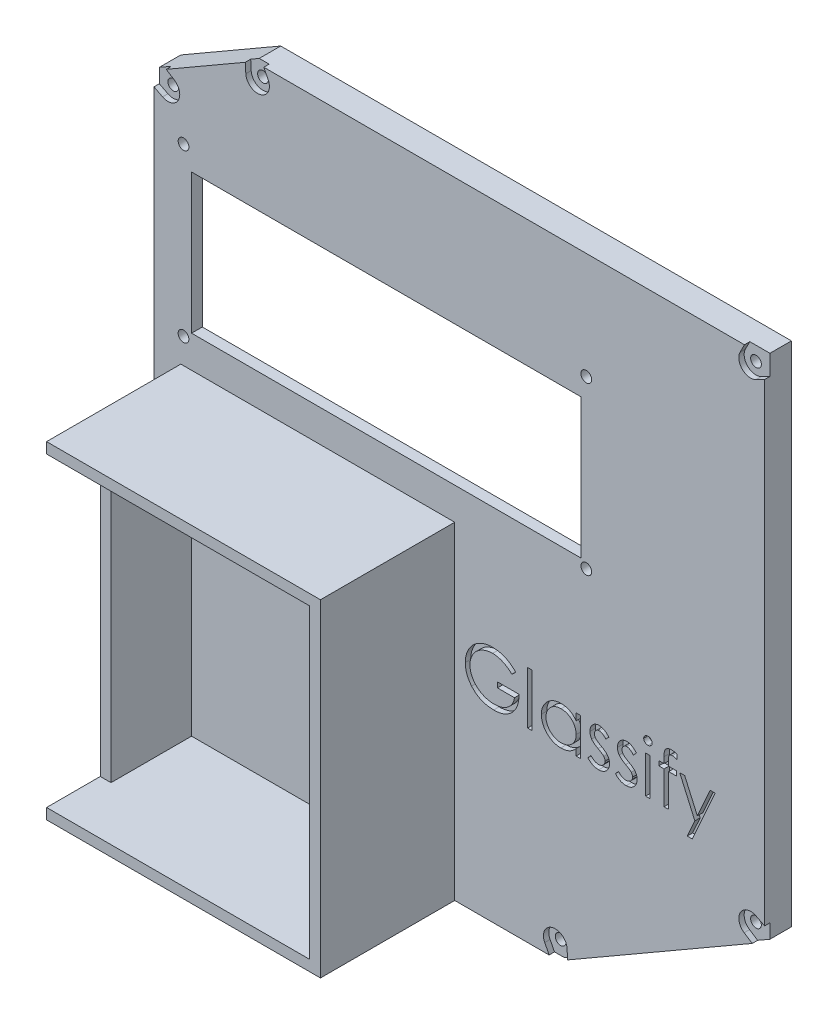
SolidWorks part; units mm, degrees
ref_plane "Front Plane" through (0, 0, 0) normal (0, 0, 1) x (1, 0, 0)
ref_plane "Top Plane" through (0, 0, 0) normal (0, 1, 0) x (1, 0, 0)
ref_plane "Right Plane" through (0, 0, 0) normal (1, 0, 0) x (0, 0, -1)
sketch "Sketch1" plane through (0, 0, 0) normal (0, 0, 1) x (1, 0, 0)
  line L6 (62.1, 287.25) -> (-33, 287.25)
  line L7 (62.1, 192.75) -> (62.1, 287.25)
  line L8 (23.8217, 170.65) -> (62.1, 192.75)
  line L9 (-51.6, 170.65) -> (23.8217, 170.65)
  line L10 (-51.6, 276.5113) -> (-51.6, 170.65)
  line L11 (-33, 287.25) -> (-51.6, 276.5113)
  line L18 (62.1, 287.25) -> (-33, 287.25)
  line L19 (62.1, 192.75) -> (62.1, 287.25)
  line L20 (23.8217, 170.65) -> (62.1, 192.75)
  line L21 (-51.6, 170.65) -> (23.8217, 170.65)
  line L22 (-51.6, 276.5113) -> (-51.6, 170.65)
  line L23 (-33, 287.25) -> (-51.6, 276.5113)
  line L24 (-50, 273.0506) -> (-50, 175.2096)
  line L25 (-34.5004, 284.5362) -> (-47.8029, 276.856)
  line L26 (57.5404, 285.65) -> (-30.3437, 285.65)
  line L27 (60.5, 196.2107) -> (60.5, 282.6904)
  line L28 (25.3221, 173.3638) -> (58.3029, 192.4053)
  line L29 (-47.0404, 172.25) -> (21.1654, 172.25)
  line L30 (-50, 273.0506) -> (-50, 175.2096)
  line L31 (-34.5004, 284.5362) -> (-47.8029, 276.856)
  line L32 (57.5404, 285.65) -> (-30.3437, 285.65)
  line L33 (60.5, 196.2107) -> (60.5, 282.6904)
  line L34 (25.3221, 173.3638) -> (58.3029, 192.4053)
  line L35 (-47.0404, 172.25) -> (21.1654, 172.25)
  circle A1 centre (-49, 173.25) radius 1
  circle A2 centre (-49, 173.25) radius 1
  circle A3 centre (-49, 275.0102) radius 1
  circle A4 centre (-49, 275.0102) radius 1
  circle A5 centre (-32.3033, 284.65) radius 1
  circle A6 centre (-32.3033, 284.65) radius 1
  circle A7 centre (59.5, 194.2511) radius 1
  circle A8 centre (59.5, 194.2511) radius 1
  circle A9 centre (59.5, 284.65) radius 1
  circle A10 centre (59.5, 284.65) radius 1
  circle A11 centre (23.125, 173.25) radius 1
  circle A12 centre (23.125, 173.25) radius 1
  arc A18 (-47.0404, 172.25) -> (-50, 175.2096) centre (-49, 173.25) ccw
  arc A19 (-50, 273.0506) -> (-47.8029, 276.856) centre (-49, 275.0102) ccw
  arc A20 (-34.5004, 284.5362) -> (-30.3437, 285.65) centre (-32.3033, 284.65) ccw
  arc A21 (57.5404, 285.65) -> (60.5, 282.6904) centre (59.5, 284.65) ccw
  arc A22 (60.5, 196.2107) -> (58.3029, 192.4053) centre (59.5, 194.2511) ccw
  arc A23 (25.3221, 173.3638) -> (21.1654, 172.25) centre (23.125, 173.25) ccw
  arc A24 (-47.0404, 172.25) -> (-50, 175.2096) centre (-49, 173.25) ccw
  arc A25 (-50, 273.0506) -> (-47.8029, 276.856) centre (-49, 275.0102) ccw
  arc A26 (-34.5004, 284.5362) -> (-30.3437, 285.65) centre (-32.3033, 284.65) ccw
  arc A27 (57.5404, 285.65) -> (60.5, 282.6904) centre (59.5, 284.65) ccw
  arc A28 (60.5, 196.2107) -> (58.3029, 192.4053) centre (59.5, 194.2511) ccw
  arc A29 (25.3221, 173.3638) -> (21.1654, 172.25) centre (23.125, 173.25) ccw
  dimension "D1" = 0
  dimension "D2" = 0
  dimension "D3" = 0
  dimension "D4" = 0
  dimension "D5" = 0
  dimension "D6" = 0
  dimension "D7" = 0
  dimension "D8" = 0
extrude "Boss-Extrude1" add sketch "Sketch1" along normal blind 3
sketch "Sketch2" plane through (0, 0, 3) normal (0, 0, 1) x (1, 0, 0)
  line L0 (23.8217, 170.65) -> (62.1, 192.75) construction
  line L1 (-51.6, 170.65) -> (23.8217, 170.65) construction
  line L2 (-51.6, 276.5113) -> (-51.6, 170.65) construction
  line L3 (-33, 287.25) -> (-51.6, 276.5113) construction
  line L4 (62.1, 287.25) -> (-33, 287.25) construction
  line L5 (62.1, 192.75) -> (62.1, 287.25) construction
  line L6 (23.8217, 170.65) -> (62.1, 192.75)
  line L7 (-51.6, 170.65) -> (23.8217, 170.65)
  line L8 (-51.6, 276.5113) -> (-51.6, 170.65)
  line L9 (-33, 287.25) -> (-51.6, 276.5113)
  line L10 (62.1, 287.25) -> (-33, 287.25)
  line L11 (62.1, 192.75) -> (62.1, 287.25)
extrude "Boss-Extrude2" add sketch "Sketch2" along normal blind 2
sketch "Sketch3" plane through (0, 0, 5) normal (0, 0, 1) x (1, 0, 0)
  line L1 (-48.6, 269.8843) -> (31.4, 269.8843) construction
  line L2 (-48.6, 269.8843) -> (-48.6, 233.8843) construction
  line L3 (-48.6, 233.8843) -> (31.4, 233.8843) construction
  line L4 (31.4, 269.8843) -> (31.4, 233.8843) construction
  line L5 (-51.6, 170.65) -> (23.8217, 170.65) construction
  line L6 (-48.6, 228.65) -> (-3.6, 228.65) construction
  line L7 (-48.6, 228.65) -> (-48.6, 173.65) construction
  line L8 (-48.6, 173.65) -> (-3.6, 173.65) construction
  line L9 (-3.6, 228.65) -> (-3.6, 173.65) construction
  line L10 (-51.6, 276.5113) -> (-51.6, 170.65) construction
  point P4 (0, 0)
  dimension "D1" = 80
  dimension "D2" = 36
  dimension "D3" = 55
  dimension "D4" = 45
  dimension "D5" = 3
  dimension "D6" = 3
sketch "Sketch4" plane through (0, 0, 3) normal (0, 0, -1) x (-1, 0, 0)
  line L1 (-27.9, 263.6343) -> (44.6, 263.6343)
  line L2 (-27.9, 263.6343) -> (-27.9, 237.6343)
  line L3 (-27.9, 237.6343) -> (44.6, 237.6343)
  line L4 (44.6, 263.6343) -> (44.6, 237.6343)
  point P4 (44.8138, 266.3299)
  point P5 (0, 0)
  point P7 (-31.4, 269.8843)
  dimension "D1" = 26
  dimension "D2" = 72.5
  dimension "D3" = 6.25
  dimension "D4" = 3.5
extrude "Cut-Extrude1" cut sketch "Sketch4" against normal up to surface (2 mm away) up to face at (1.9703, 230.8435, 5)
sketch "Sketch5" plane through (0, 0, 3) normal (0, 0, -1) x (-1, 0, 0)
  line L0 (48.6, 269.8843) -> (48.6, 233.8843) construction
  line L1 (-31.4, 269.8843) -> (-31.4, 233.8843) construction
  line L2 (48.6, 269.8843) -> (-31.4, 269.8843) construction
  line L3 (48.6, 233.8843) -> (-31.4, 233.8843) construction
  line L4 (48.6, 228.65) -> (3.6, 228.65) construction
  line L5 (48.6, 228.65) -> (48.6, 173.65) construction
  line L6 (48.6, 173.65) -> (3.6, 173.65) construction
  line L7 (3.6, 228.65) -> (3.6, 173.65) construction
  line L8 (48.6, 228.65) -> (3.6, 228.65) construction
  line L9 (48.6, 228.65) -> (48.6, 173.65) construction
  line L10 (48.6, 173.65) -> (3.6, 173.65) construction
  line L11 (3.6, 228.65) -> (3.6, 173.65) construction
  line L13 (6.1, 226.15) -> (31.1, 226.15)
  line L14 (6.1, 226.15) -> (6.1, 224.15)
  line L15 (6.1, 224.15) -> (31.1, 224.15)
  line L16 (31.1, 226.15) -> (31.1, 224.15)
  circle A0 centre (46.1, 267.3843) radius 1
  circle A1 centre (46.1, 236.3843) radius 1
  circle A2 centre (-28.9, 267.3843) radius 1
  circle A3 centre (-28.9, 236.3843) radius 1
  dimension "D5" = 2
  dimension "D1" = 2.5
  dimension "D2" = 2.5
  dimension "D3" = 2.5
  dimension "D4" = 2.5
  dimension "D6" = 25
  dimension "D7" = 2
  dimension "D8" = 2.5
  dimension "D9" = 2.5
extrude "Cut-Extrude2" cut sketch "Sketch5" against normal up to surface (2 mm away) up to face at (-8.35, 250.6343, 5)
sketch "Sketch6" plane through (0, 0, 5) normal (0, 0, 1) x (1, 0, 0)
  line L0 (-51.6, 170.65) -> (23.8217, 170.65) construction
  line L2 (-51.6, 276.5113) -> (-51.6, 170.65) construction
  line L4 (-43.6, 173.65) -> (1.4, 173.65) construction
  line L5 (1.4, 228.65) -> (1.4, 173.65) construction
  line L6 (-43.6, 228.65) -> (1.4, 228.65) construction
  line L7 (-43.6, 228.65) -> (-43.6, 173.65) construction
  line L8 (-44.6, 172.65) -> (2.4, 172.65)
  line L9 (2.4, 229.65) -> (2.4, 172.65)
  line L10 (-44.6, 229.65) -> (2.4, 229.65)
  line L11 (-44.6, 229.65) -> (-44.6, 172.65)
  line L12 (-46.6, 231.65) -> (4.4, 231.65)
  line L13 (4.4, 231.65) -> (4.4, 170.65)
  line L14 (-46.6, 170.65) -> (4.4, 170.65)
  line L15 (-46.6, 231.65) -> (-46.6, 170.65)
  dimension "D3" = 45
  dimension "D4" = 55
  dimension "D5" = 5
  dimension "D1" = 1
  dimension "D2" = 2
extrude "Boss-Extrude3" add sketch "Sketch6" along normal blind 25
sketch "Sketch7" plane through (-51.6, 0, 0) normal (-1, 0, 0) x (0, 0, 1)
  line L0 (30, 172.65) -> (30, 229.65) construction
  line L1 (30, 172.65) -> (30, 229.65)
  line L2 (30, 229.65) -> (20, 229.65)
  line L3 (20, 229.65) -> (20, 172.65)
  line L4 (20, 172.65) -> (30, 172.65)
  dimension "D1" = 10
extrude "Cut-Extrude3" cut sketch "Sketch7" against normal blind 25
sketch "Sketch8" plane through (0, 0, 5) normal (0, 0, 1) x (1, 0, 0)
  line L0 (60.5, 196.2107) -> (62.1, 195.3942)
  line L1 (62.1, 192.75) -> (62.1, 287.25) construction
  line L2 (62.1, 195.3942) -> (62.1, 192.75)
  line L3 (62.1, 192.75) -> (59.8101, 191.4279)
  line L4 (23.8217, 170.65) -> (62.1, 192.75) construction
  line L5 (59.8101, 191.4279) -> (58.3029, 192.4053)
  line L6 (25.3221, 173.3638) -> (25.415, 171.5699)
  line L7 (25.415, 171.5699) -> (23.8217, 170.65)
  line L8 (23.8217, 170.65) -> (21.9819, 170.65)
  line L9 (4.4, 170.65) -> (23.8217, 170.65) construction
  line L10 (21.9819, 170.65) -> (21.1654, 172.25)
  line L11 (-47.0404, 172.25) -> (-47.8569, 170.65)
  line L18 (-47.0404, 172.25) -> (21.1654, 172.25)
  line L19 (-50, 273.0506) -> (-50, 175.2096)
  line L20 (-34.5004, 284.5362) -> (-47.8029, 276.856)
  line L21 (57.5404, 285.65) -> (-30.3437, 285.65)
  line L22 (60.5, 196.2107) -> (60.5, 282.6904)
  line L23 (25.3221, 173.3638) -> (58.3029, 192.4053)
  line L30 (-51.6, 170.65) -> (23.8217, 170.65) construction
  line L31 (-47.8569, 170.65) -> (-51.6, 170.65)
  line L32 (-51.6, 170.65) -> (-51.6, 174.3931)
  line L33 (-51.6, 276.5113) -> (-51.6, 170.65) construction
  line L34 (-51.6, 174.3931) -> (-50, 175.2096)
  line L35 (-47.8029, 276.856) -> (-49.3101, 277.8334)
  line L36 (-33, 287.25) -> (-51.6, 276.5113) construction
  line L37 (-49.3101, 277.8334) -> (-51.6, 276.5113)
  line L38 (-51.6, 276.5113) -> (-51.6, 273.8671)
  line L39 (-51.6, 276.5113) -> (-51.6, 170.65) construction
  line L40 (-51.6, 273.8671) -> (-50, 273.0506)
  line L41 (-30.3437, 285.65) -> (-31.1602, 287.25)
  line L42 (62.1, 287.25) -> (-33, 287.25) construction
  line L43 (-31.1602, 287.25) -> (-33, 287.25)
  line L44 (-33, 287.25) -> (-34.5933, 286.3301)
  line L45 (-51.6, 276.5113) -> (-33, 287.25) construction
  line L46 (-34.5933, 286.3301) -> (-34.5004, 284.5362)
  line L47 (57.5404, 285.65) -> (58.3569, 287.25)
  line L48 (58.3569, 287.25) -> (62.1, 287.25)
  line L49 (62.1, 287.25) -> (62.1, 283.5069)
  line L50 (62.1, 283.5069) -> (60.5, 282.6904)
  circle A1 centre (-49, 275.0102) radius 1
  circle A2 centre (-49, 275.0102) radius 1
  circle A3 centre (-49, 173.25) radius 1
  circle A4 centre (-49, 173.25) radius 1
  circle A5 centre (23.125, 173.25) radius 1
  circle A6 centre (23.125, 173.25) radius 1
  circle A7 centre (59.5, 284.65) radius 1
  circle A8 centre (59.5, 284.65) radius 1
  circle A9 centre (59.5, 194.2511) radius 1
  circle A10 centre (59.5, 194.2511) radius 1
  circle A11 centre (-32.3033, 284.65) radius 1
  circle A12 centre (-32.3033, 284.65) radius 1
  arc A18 (-47.0404, 172.25) -> (-50, 175.2096) centre (-49, 173.25) ccw
  arc A19 (-50, 273.0506) -> (-47.8029, 276.856) centre (-49, 275.0102) ccw
  arc A20 (-34.5004, 284.5362) -> (-30.3437, 285.65) centre (-32.3033, 284.65) ccw
  arc A21 (57.5404, 285.65) -> (60.5, 282.6904) centre (59.5, 284.65) ccw
  arc A22 (60.5, 196.2107) -> (58.3029, 192.4053) centre (59.5, 194.2511) ccw
  arc A23 (25.3221, 173.3638) -> (21.1654, 172.25) centre (23.125, 173.25) ccw
  arc A24 (-47.0404, 172.25) -> (-50, 175.2096) centre (-49, 173.25) ccw
  arc A25 (-50, 273.0506) -> (-47.8029, 276.856) centre (-49, 275.0102) ccw
  arc A26 (-34.5004, 284.5362) -> (-30.3437, 285.65) centre (-32.3033, 284.65) ccw
  arc A27 (57.5404, 285.65) -> (60.5, 282.6904) centre (59.5, 284.65) ccw
  arc A28 (60.5, 196.2107) -> (58.3029, 192.4053) centre (59.5, 194.2511) ccw
  arc A29 (25.3221, 173.3638) -> (21.1654, 172.25) centre (23.125, 173.25) ccw
  text T0 "Glassify" font "Century Gothic" height in points 36
  dimension "D1" = 0
  dimension "D2" = 0
  dimension "D4" = 0
  dimension "D5" = 0
  dimension "D6" = 0
  dimension "D7" = 0
  dimension "D8" = 0
extrude "Cut-Extrude4" cut sketch "Sketch8" against normal blind 1
extrude "Cut-Extrude5" cut sketch "Sketch8<2>" against normal through all both and the other way through all contours A4 | A10 | A6 | A2 | A12 | A8 region at (-49, 173.25, 5)
sketch "Sketch8<2>" plane through (0, 0, 5) normal (0, 0, 1) x (1, 0, 0) same geometry as "Sketch8"
